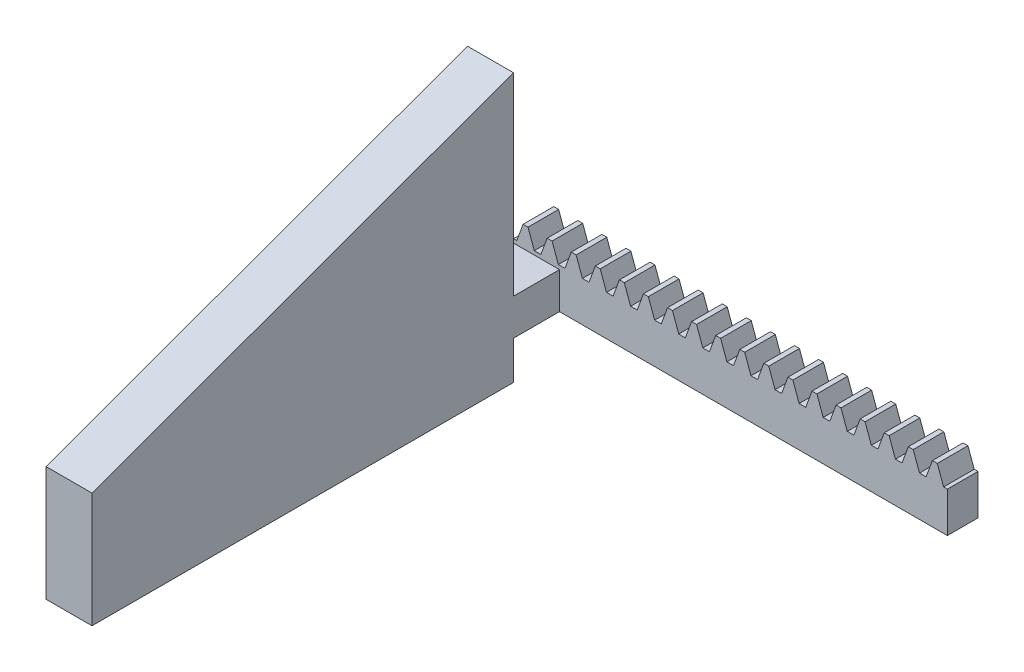
SolidWorks part; units mm, degrees
extrude "Blank" add sketch "BlankSke" against normal blind 8
sketch "BlankSke" plane through (0, 0, 0) normal (0, 0, 1) x (1, 0, 0)
  line L1 (0, 0) -> (120, 0)
  line L2 (0, 0) -> (0, 16)
  line L3 (0, 16) -> (120, 16)
  line L4 (120, 0) -> (120, 16)
  dimension "Length" = 120
ref_plane "Plane1" through (0, 0, 0) normal (0, 0, 1) x (1, 0, 0)
ref_plane "Plane2" through (0, 0, 0) normal (0, 1, 0) x (1, 0, 0)
ref_plane "Plane3" through (0, 0, 0) normal (1, 0, 0) x (0, 0, -1)
sketch "HoldingSke" plane through (0, 0, 0) normal (0, 1, 0) x (1, 0, 0)
  line L0 (0, 0) -> (0.0696, 0.4951)
  line L1 (-15, 0) -> (100, 0) construction
  line L2 (0, 0) -> (-2.1039, 2.3779)
  line L3 (0, 0) -> (-11.863, 4.5341)
  line L4 (0, 0) -> (8.0624, 3.0949)
  line L5 (0, 0) -> (-23.7986, -8.8762)
  line L6 (0, 0) -> (-10.5278, -7.1032)
  line L9 (-71.009, 38.7566) -> (41.7541, 79.799)
  line L10 (-76.2, 4.3779) -> (-62.2, 4.3779)
  line L11 (0, 0) -> (-8, 0)
  line L12 (-76.2, 101.6) -> (-76.133, 101.6)
  line L13 (24.9733, 27.94) -> (52.9518, 28.4284)
  line L14 (24.9733, 27.94) -> (24.9743, 27.94)
  line L15 (24.9733, 27.94) -> (100.4006, 29.5858)
  circle A0 centre (0, 0) radius 19.05
  circle A1 centre (0, 0) radius 7
  circle A2 centre (0, 0) radius 12.7
  dimension "Num_teeth" = 21
  dimension "Width" = 8
  dimension "Length" = 120
  dimension "Pitch_height" = 14
sketch "TooCutSkeIll" plane through (0, 0, 0) normal (0, 0, 1) x (1, 0, 0)
  line L0 (-2.4806, 15.9474) -> (-0.9819, 11.8296)
  line L1 (-0.5111, 11.5) -> (0.5111, 11.5)
  line L2 (0.9819, 11.8296) -> (2.4806, 15.9474)
  line L3 (120, 16) -> (0, 16) construction
  line L4 (0, 0) -> (0, 64.897) construction
  line L5 (-13.208, 14) -> (12.954, 14) construction
  line L6 (0, 0) -> (120, 0) construction
  line L7 (1.7718, 14) -> (1.7718, 48.7463) construction
  line L8 (-1.7718, 14) -> (-1.7718, 48.7463) construction
  line L9 (2.5558, 16) -> (2.5558, 16.0254)
  line L10 (-2.5558, 16) -> (-2.5558, 16.0254)
  line L11 (-2.5558, 16.0254) -> (2.5558, 16.0254)
  arc A0 (0.5111, 11.5) -> (0.9819, 11.8296) centre (0.5111, 12.001) ccw
  arc A1 (-0.9819, 11.8296) -> (-0.5111, 11.5) centre (-0.5111, 12.001) ccw
  arc A2 (2.5558, 16) -> (2.4806, 15.9474) centre (2.5558, 15.92) ccw
  arc A3 (-2.4806, 15.9474) -> (-2.5558, 16) centre (-2.5558, 15.92) ccw
  dimension "Addendum_plus" = 2.0254
  dimension "Pitch_height" = 14
  dimension "Pressure_angle" = 20
  dimension "Gap_width" = 3.5436
  dimension "Dedendum" = 2.5
extrude "ToothCutIll" [suppressed] cut sketch "TooCutSkeIll" against normal through all
sketch "TooCutSkeSim" plane through (0, 0, 0) normal (0, 0, 1) x (1, 0, 0)
  line L0 (0.8619, 11.5) -> (-0.8619, 11.5)
  line L1 (2.509, 16.0254) -> (0.8619, 11.5)
  line L2 (0, 17.4625) -> (0, 53.467) construction
  line L3 (2.509, 16.0254) -> (-2.509, 16.0254)
  line L6 (-2.509, 16.0254) -> (-0.8619, 11.5)
  line L9 (-1.7718, 14) -> (1.7718, 14) construction
  line L10 (0, 0) -> (120, 0) construction
  line L11 (1.7718, 14) -> (1.7718, 53.467) construction
  line L12 (-1.7718, 14) -> (-1.7718, 53.467) construction
  dimension "Addendum_plus" = 2.0254
  dimension "Pitch_height" = 14
  dimension "Pressure_angle" = 20
  dimension "Gap_width" = 3.5436
  dimension "Dedendum" = 2.5
extrude "ToothCutSim" cut sketch "TooCutSkeSim" against normal through all
pattern_linear "TeethCuts" count 21 spacing 6.2832 along (1, 0, 0) of "ToothCutIll", "ToothCutSim"
sketch "Sketch1" plane through (120, 0, 0) normal (1, 0, 0) x (0, 0, -1)
  line L0 (0, 1) -> (8, 1)
  line L1 (0, 0) -> (0, 11.5) construction
  line L2 (8, 0) -> (8, 11.5) construction
  line L3 (8, 1) -> (8, 0)
  line L4 (8, 0) -> (0, 0)
  line L5 (0, 0) -> (0, 1)
  dimension "D1" = 1
extrude "Cut-Extrude1" cut sketch "Sketch1" against normal through all
sketch "Sketch2" plane through (120, 0, 0) normal (1, 0, 0) x (0, 0, -1)
  line L0 (0, 1) -> (-12, 1)
  line L1 (-12, 1) -> (-12, -9)
  line L2 (-12, -9) -> (-122, -9)
  line L3 (-122, -9) -> (-122, 21)
  line L4 (-122, 21) -> (-12, 61)
  line L5 (-12, 61) -> (-12, 10)
  line L6 (-12, 10) -> (0, 10)
  line L7 (0, 1) -> (0, 11.5) construction
  line L8 (0, 10) -> (0, 1)
  dimension "D1" = 110
  dimension "D2" = 30
  dimension "D3" = 9
  dimension "D4" = 70
  dimension "D5" = 10
  dimension "D6" = 12
sketch "Sketch3" plane through (0, 0, 0) normal (-1, 0, 0) x (0, 0, 1)
  line L0 (0, 1) -> (12, 1)
  line L1 (12, 1) -> (12, -9)
  line L2 (12, -9) -> (122, -9)
  line L3 (122, -9) -> (122, 21)
  line L4 (122, 21) -> (12, 61)
  line L5 (12, 61) -> (12, 10.5)
  line L6 (12, 10.5) -> (0, 10.5)
  line L7 (0, 11.5) -> (0, 1) construction
  line L8 (0, 10.5) -> (0, 1)
  dimension "D1" = 9.5
  dimension "D2" = 12
  dimension "D3" = 10
  dimension "D4" = 110
  dimension "D5" = 70
  dimension "D6" = 30
extrude "Boss-Extrude2" add sketch "Sketch3" against normal blind 12
sketch "Sketch4" plane through (0, 0, -8) normal (0, 0, -1) x (-1, 0, 0)
  line L0 (-120, 11.5) -> (-118.5186, 11.5)
  line L1 (-113.9592, 11.5) -> (-113.2187, 11.5)
  line L2 (-112.2355, 11.5) -> (-113.9592, 11.5) construction
  line L3 (-113.2187, 11.5) -> (-113.2187, 1)
  line L4 (0, 1) -> (-120, 1) construction
  line L5 (-113.2187, 1) -> (-120, 1)
  line L6 (-120, 1) -> (-120, 11.5)
  line L7 (-118.5186, 11.5) -> (-116.8808, 16)
  line L8 (-116.8808, 16) -> (-115.5971, 16)
  line L9 (-115.5971, 16) -> (-113.9592, 11.5)
  dimension "D1" = 0.7405
extrude "Cut-Extrude2" cut sketch "Sketch4" against normal through all
equation "' \"Module@HoldingSke\" = 6.35"
equation "' \"Num_teeth@HoldingSke\" = 12"
equation "' \"Ap@HoldingSke\" =  20"
equation "' \"Ap@HoldingSke\" = 20"
equation "' \"Width@HoldingSke\" = 0.25 * 25.4"
equation "' \"Show_teeth@HoldingSke\" = 500"
equation "' \"Backlash@HoldingSke\" = 0.009 * 25.4"
equation "' \"Addendum_fac@HoldingSke\" = 1.0"
equation "' \"Dedendum_fac@HoldingSke\" = 1.25"
equation "' \"Dedendum_add@HoldingSke\" = 0.00005 * 25.4"
equation "' \"Clearance_fac@HoldingSke\" = 0.25"
equation "' \"Pitch_height@HoldingSke\" = 1 * 25.4"
equation "' \"Length@HoldingSke\" = 4.71 * 25.4"
equation "\"Pitch@HoldingSke\" = 1 / \"Module@HoldingSke\""
equation "\"MPH@HoldingSke\" = \"Dedendum_fac@HoldingSke\" / \"Pitch@HoldingSke\" + 2 * \"Dedendum_add@HoldingSke\" + 0.002 * 25.4"
equation "\"MPH@HoldingSke\" = ((sgn( \"MPH@HoldingSke\" - \"Pitch_height@HoldingSke\")+1)*( \"MPH@HoldingSke\" - \"Pitch_height@HoldingSke\"))/2 + \"Pitch_height@HoldingSke\""
equation "\"Blank_height@BlankSke\" = \"Pitch_height@HoldingSke\" + \"Addendum_fac@HoldingSke\"  / \"Pitch@HoldingSke\" "
equation "\"Length@BlankSke\" =  \"Length@HoldingSke\""
equation "\"Face_width@Blank\" = \"Width@HoldingSke\""
equation "\"Pressure_angle@TooCutSkeIll\" = \"Ap@HoldingSke\""
equation "\"Addendum_plus@TooCutSkeIll\" =  \"Addendum_fac@HoldingSke\"  / \"Pitch@HoldingSke\" + 0.001 *25.4"
equation "\"Dedendum@TooCutSkeIll\" = \"Dedendum_fac@HoldingSke\"  / \"Pitch@HoldingSke\""
equation "\"Pitch_height@TooCutSkeIll\" =  \"MPH@HoldingSke\""
equation "\"Gap_width@TooCutSkeIll\" = 3.14159265 / 2 / \"Pitch@HoldingSke\" + 6 * \"Backlash@HoldingSke\""
equation "\"Pressure_angle@TooCutSkeSim\" = \"Ap@HoldingSke\""
equation "\"Addendum_plus@TooCutSkeSim\" =  \"Addendum_fac@HoldingSke\"  / \"Pitch@HoldingSke\" + 0.001 * 25.4"
equation "\"Dedendum@TooCutSkeSim\" = \"Dedendum_fac@HoldingSke\"  / \"Pitch@HoldingSke\""
equation "\"Pitch_height@TooCutSkeSim\" =  \"MPH@HoldingSke\""
equation "\"Gap_width@TooCutSkeSim\" = 3.14159265 / 2 / \"Pitch@HoldingSke\" + 6 * \"Backlash@HoldingSke\""
equation "\"Root_fillet@TooCutSkeIll\" = \"Clearance_fac@HoldingSke\" / \"Pitch@HoldingSke\" + \"Dedendum_add@HoldingSke\""
equation "\"Break_rad@TooCutSkeIll\" = 0.02 / \"Pitch@HoldingSke\" * 2"
equation "\"Linear_pitch@TeethCuts\" = 3.14159265 / \"Pitch@HoldingSke\""
equation "\"Num_teeth@HoldingSke\" = int( ( \"Length@HoldingSke\" + 0 ) / (3.14159265 / \"Pitch@HoldingSke\")) + 0.9999  + 1"
equation " \"Num_teeth@TeethCuts\" = int( \"Show_teeth@HoldingSke\" ) + 1"
equation " \"Num_teeth@TeethCuts\" = ((sgn( \"Num_teeth@TeethCuts\" - \"Num_teeth@HoldingSke\" )-1)*( \"Num_teeth@TeethCuts\" - \"Num_teeth@HoldingSke\" ))/-2+ \"Num_teeth@HoldingSke\""
equation " \"Num_teeth@TeethCuts\" = ((sgn( \"Num_teeth@TeethCuts\" - 2.0)+1)*( \"Num_teeth@TeethCuts\" - 2.0))/2 +2.0"
